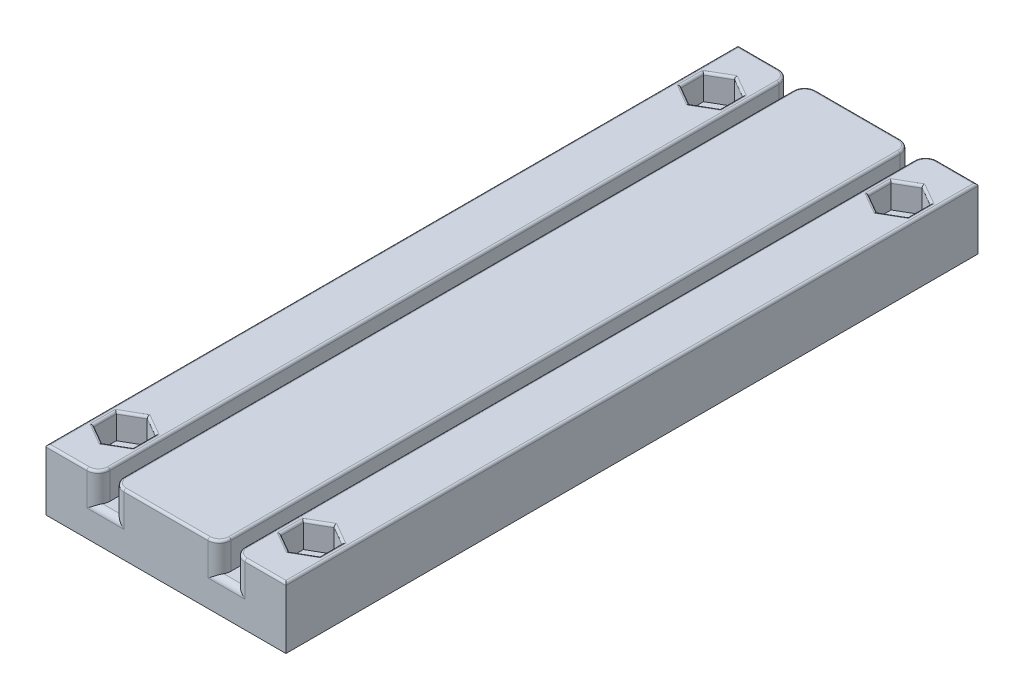
SolidWorks part; units mm, degrees
ref_plane "Front Plane" through (0, 0, 0) normal (0, 0, 1) x (1, 0, 0)
ref_plane "Top Plane" through (0, 0, 0) normal (0, 1, 0) x (1, 0, 0)
ref_plane "Right Plane" through (0, 0, 0) normal (1, 0, 0) x (0, 0, -1)
sketch "Sketch1" plane through (0, 0, 0) normal (0, 0, 1) x (1, 0, 0)
  line L0 (0, 0) -> (11.5341, 0)
  line L1 (11.5341, 0) -> (11.5341, -6.35)
  line L2 (11.5341, -6.35) -> (14.6342, -6.35)
  line L3 (14.6342, -6.35) -> (14.6342, 0)
  line L4 (14.6342, 0) -> (38.2041, 0)
  line L5 (38.2041, 0) -> (38.2041, -6.35)
  line L6 (38.2041, -6.35) -> (41.3042, -6.35)
  line L7 (41.3042, -6.35) -> (41.3042, 0)
  line L8 (41.3042, 0) -> (52.8384, 0)
  line L9 (52.8384, 0) -> (52.8384, -13.462)
  line L10 (52.8384, -13.462) -> (0, -13.462)
  line L11 (0, -13.462) -> (0, 0)
  dimension "D1" = 11.5341
  dimension "D2" = 3.1001
  dimension "D3" = 23.5699
  dimension "D4" = 3.1001
  dimension "D5" = 11.5341
  dimension "D6" = 6.35
  dimension "D7" = 13.462
extrude "Boss-Extrude1" add sketch "Sketch1" along normal blind 152.4
sketch "Sketch2" plane through (0, 0, 0) normal (0, 1, 0) x (1, 0, 0)
  line L0 (0, -11.5341) -> (52.8384, -11.5341)
  line L1 (0, -152.4) -> (0, 0) construction
  line L2 (52.8384, -152.4) -> (52.8384, 0) construction
  line L3 (11.5341, 0) -> (0, 0) construction
  line L4 (0, -140.8659) -> (52.8384, -140.8659)
  line L5 (52.8384, -152.4) -> (41.3042, -152.4) construction
  line L6 (5.7671, -152.4) -> (5.7671, -146.888) construction
  line L8 (47.0713, -152.4) -> (47.0713, -146.3823) construction
  dimension "D1" = 11.5341
  dimension "D2" = 11.5341
sketch "Sketch3" plane through (0, 0, 0) normal (0, 1, 0) x (1, 0, 0)
  line L0 (5.7671, -200152.4) -> (5.7671, 199853.112) construction
  line L3 (47.0713, -200152.4) -> (47.0713, 199853.6177) construction
  line L4 (0, -11.5341) -> (52.8384, -11.5341) construction
  line L5 (0, -140.8659) -> (52.8384, -140.8659) construction
  circle A0 centre (5.7671, -11.542) radius 1.8987
  circle A1 centre (47.0713, -11.5341) radius 1.8986
  circle A2 centre (5.7671, -140.8659) radius 1.8987
  circle A3 centre (47.0713, -140.8659) radius 1.8987
extrude "Cut-Extrude1" cut sketch "Sketch3" against normal up to surface (13.462 mm away) up to face at (26.4192, -13.462, 76.2)
sketch "Sketch4" plane through (0, 0, 0) normal (0, 1, 0) x (1, 0, 0)
  line L0 (41.3042, -152.4) -> (41.3042, 0) construction
  line L1 (10.0851, -9.049) -> (5.7671, -6.556)
  line L2 (5.7671, -6.556) -> (1.4491, -9.049)
  line L3 (1.4491, -9.049) -> (1.4491, -14.035)
  line L4 (1.4491, -14.035) -> (5.7671, -16.528)
  line L5 (5.7671, -16.528) -> (10.0851, -14.035)
  line L6 (10.0851, -14.035) -> (10.0851, -9.049)
  line L7 (51.3893, -9.0411) -> (47.0713, -6.5481)
  line L8 (47.0713, -6.5481) -> (42.7533, -9.0411)
  line L9 (42.7533, -9.0411) -> (42.7533, -14.0271)
  line L10 (42.7533, -14.0271) -> (47.0713, -16.5201)
  line L11 (47.0713, -16.5201) -> (51.3893, -14.0271)
  line L12 (51.3893, -14.0271) -> (51.3893, -9.0411)
  line L13 (11.5341, -152.4) -> (11.5341, 0) construction
  line L14 (41.3042, -152.4) -> (41.3042, 0) construction
  line L15 (10.0851, -143.3589) -> (10.0851, -138.3729)
  line L16 (10.0851, -138.3729) -> (5.7671, -135.8799)
  line L17 (5.7671, -135.8799) -> (1.4491, -138.3729)
  line L18 (1.4491, -138.3729) -> (1.4491, -143.3589)
  line L19 (1.4491, -143.3589) -> (5.7671, -145.8519)
  line L20 (5.7671, -145.8519) -> (10.0851, -143.3589)
  line L21 (47.0713, -145.9406) -> (51.3509, -143.4697)
  line L22 (51.3509, -143.4697) -> (51.3509, -138.5281)
  line L23 (51.3509, -138.5281) -> (47.0713, -136.0573)
  line L24 (47.0713, -136.0573) -> (42.7917, -138.5281)
  line L25 (42.7917, -138.5281) -> (42.7917, -143.4697)
  line L26 (42.7917, -143.4697) -> (47.0713, -145.9406)
  circle A0 centre (5.7671, -11.542) radius 4.318 construction
  circle A1 centre (47.0713, -11.5341) radius 4.318 construction
  circle A2 centre (5.7671, -140.8659) radius 4.318 construction
  circle A3 centre (47.0713, -140.9989) radius 4.2796 construction
  dimension "D1" = 8.636
  dimension "D2" = 8.636
  dimension "D3" = 8.636
  dimension "D4" = 8.5592
extrude "Cut-Extrude2" cut sketch "Sketch4" against normal blind 5.588
fillet "Fillet2" radius 0.508 36 edges at (49.2111, 0, 144.7052) (44.9315, 0, 144.7052) (51.3509, 0, 140.9989) (42.7917, 0, 140.9989) (44.9315, 0, 137.2927) (49.2111, 0, 137.2927) (10.0851, 0, 140.8659) (7.9261, 0, 137.1264) (3.6081, 0, 137.1264) (1.4491, 0, 140.8659) (3.6081, 0, 144.6054) (7.9261, 0, 144.6054) (5.7671, 0, 152.4) (26.4192, 0, 152.4) (47.0713, 0, 152.4) (51.3893, 0, 11.5341) (49.2303, 0, 15.2736) (42.7533, 0, 11.5341) (44.9123, 0, 15.2736) (44.9123, 0, 7.7946) (49.2303, 0, 7.7946) (52.8384, 0, 76.2) (47.0713, 0, 0) (41.3042, 0, 76.2) (38.2041, 0, 76.2) (26.4192, 0, 0) (14.6342, 0, 76.2) (11.5341, 0, 76.2) (1.4491, 0, 11.542) (3.6081, 0, 15.2815) (7.9261, 0, 15.2815) (10.0851, 0, 11.542) (7.9261, 0, 7.8025) (3.6081, 0, 7.8025) (5.7671, 0, 0) (0, 0, 76.2)
fillet "Fillet3" radius 2.54 16 edges at (11.3854, -0.1488, 0.1488) (14.783, -0.1488, 0.1488) (38.0554, -0.1488, 0.1488) (41.453, -0.1488, 0.1488) (11.3854, -0.1488, 152.2512) (14.783, -0.1488, 152.2512) (38.0554, -0.1488, 152.2512) (41.453, -0.1488, 152.2512) (41.3042, -3.429, 152.4) (38.2041, -3.429, 152.4) (14.6342, -3.429, 152.4) (11.5341, -3.429, 152.4) (41.3042, -3.429, 0) (38.2041, -3.429, 0) (14.6342, -3.429, 0) (11.5341, -3.429, 0)
fillet "Fillet4" radius 1.27 4 edges at (39.7542, -6.35, 152.4) (13.0842, -6.35, 152.4) (13.0842, -6.35, 0) (39.7542, -6.35, 0)
sketch "Sketch5" plane through (0, -13.462, 0) normal (0, -1, 0) x (1, 0, 0)
  line L0 (0, 114.3) -> (52.8384, 114.3) construction
  line L1 (0, 76.2) -> (52.8384, 76.2) construction
  line L2 (0, 152.4) -> (0, 0) construction
  line L3 (52.8384, 152.4) -> (52.8384, 0) construction
  line L4 (0, 0) -> (52.8384, 76.2) construction
  line L5 (52.8384, 76.2) -> (0, 152.4) construction
  line L6 (52.8384, 0) -> (0, 76.2) construction
  line L7 (0, 76.2) -> (52.8384, 152.4) construction
  line L9 (33.4416, 4.7625) -> (19.3967, 4.7625)
  line L10 (33.4416, 4.7625) -> (33.4416, 71.4375)
  line L11 (33.4416, 71.4375) -> (19.3967, 71.4375)
  line L12 (19.3967, 4.7625) -> (19.3967, 71.4375)
  line L13 (33.4416, 4.7625) -> (19.3967, 71.4375) construction
  line L14 (33.4416, 71.4375) -> (19.3967, 4.7625) construction
  line L15 (33.4416, 80.9625) -> (19.3967, 80.9625)
  line L16 (33.4416, 80.9625) -> (33.4416, 147.6375)
  line L17 (33.4416, 147.6375) -> (19.3967, 147.6375)
  line L18 (19.3967, 80.9625) -> (19.3967, 147.6375)
  line L19 (33.4416, 80.9625) -> (19.3967, 147.6375) construction
  line L20 (33.4416, 147.6375) -> (19.3967, 80.9625) construction
  line L21 (0, 38.1) -> (52.8384, 38.1) construction
  point P11 (26.4192, 38.1)
  point P19 (26.4192, 114.3)
  dimension "D1" = 4.7625
  dimension "D2" = 4.7625
  dimension "D3" = 14.0449
extrude "Cut-Extrude3" cut sketch "Sketch5" against normal blind 9.398
fillet "Fillet6" radius 2.54 8 edges at (19.3967, -8.763, 80.9625) (19.3967, -8.763, 4.7625) (19.3967, -8.763, 71.4375) (19.3967, -8.763, 147.6375) (33.4416, -8.763, 4.7625) (33.4416, -8.763, 80.9625) (33.4416, -8.763, 71.4375) (33.4416, -8.763, 147.6375)
fillet "Fillet7" radius 2.54 16 edges at (20.1407, -4.064, 81.7064) (26.4192, -4.064, 80.9625) (32.6977, -4.064, 81.7064) (33.4416, -4.064, 114.3) (32.6977, -4.064, 146.8936) (26.4192, -4.064, 147.6375) (20.1407, -4.064, 146.8936) (19.3967, -4.064, 114.3) (20.1407, -4.064, 70.6936) (19.3967, -4.064, 38.1) (20.1407, -4.064, 5.5064) (26.4192, -4.064, 4.7625) (32.6977, -4.064, 5.5064) (33.4416, -4.064, 38.1) (32.6977, -4.064, 70.6936) (26.4192, -4.064, 71.4375)
